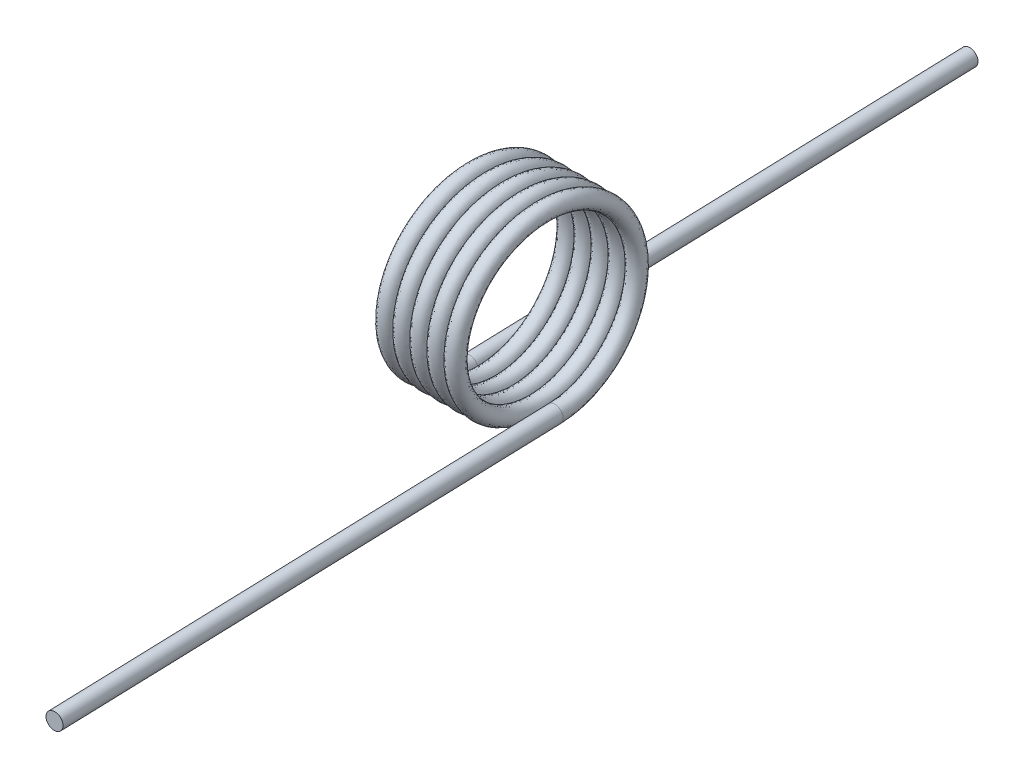
SolidWorks part; units mm, degrees
ref_plane "Front" through (0, 0, 0) normal (0, 0, 1) x (1, 0, 0)
ref_plane "Top" through (0, 0, 0) normal (0, 1, 0) x (1, 0, 0)
ref_plane "Right" through (0, 0, 0) normal (1, 0, 0) x (0, 0, -1)
sketch "Sketch1" plane through (0, 0, 0) normal (1, 0, 0) x (0, 0, -1)
  line L0 (0, 0) -> (0, -3.8354) construction
  line L1 (0, -3.8354) -> (0, -4.2418) construction
  line L2 (0, -4.2418) -> (0, -4.6482) construction
  circle A0 centre (0, 0) radius 3.8354 construction
  circle A1 centre (0, 0) radius 4.6482 construction
  circle A2 centre (0, 0) radius 4.2418
  circle A3 centre (0, -4.2418) radius 0.4064 construction
  circle A4 centre (0, 0) radius 3.175 construction
  dimension "Wire Dia" = 0.8128
  dimension "Spring OD" = 9.2964
  dimension "Max Rod OD" = 6.35
curve "Helix/Spiral1" pitch 0.8382 height 4.191 turns 5
ref_plane "Plane1" through (0, -4.2418, 0) normal (0.0314, 0, 0.9995) x (0.9995, 0, -0.0314)
sketch "Sketch2" plane through (0, -4.2418, 0) normal (0.0314, 0, 0.9995) x (0.9995, 0, -0.0314)
  circle A0 centre (0, 0) radius 0.4064
  dimension "D1" = 0.8128
sweep "Sweep1" add profiles "Sketch2" path "Helix/Spiral1"
sketch "Sketch3" plane through (0, 0, 0) normal (-0.0314, 0, -0.9995) x (-0.9995, 0, 0.0314)
  circle A1 centre (0, -4.2418) radius 0.4064
  circle A2 centre (0, -4.2418) radius 0.4064
  dimension "D1" = 0
extrude "Extrude1" add sketch "Sketch3" along normal blind 25.4
sketch "Sketch4" plane through (0.0041, 0, 0.1317) normal (0.0314, 0, 0.9995) x (0.9958, -0.0856, -0.0313)
  circle A1 centre (4.5367, -3.8676) radius 0.4064
  circle A2 centre (4.5367, -3.8676) radius 0.4064
  dimension "D1" = 0
extrude "Extrude2" add sketch "Sketch4" along normal blind 25.4
sketch "Sketch5" plane through (0, 0, 0) normal (1, 0, 0) x (0, 0, -1)
  circle A0 centre (0, 0) radius 3.175 construction
  circle A1 centre (0, 0) radius 3.175
equation "\"D4@Helix/Spiral1\"=\"Wire Dia@Sketch1\"+.001"
equation "\"D1@Sketch2\"=\"Wire Dia@Sketch1\""
equation "\"D1@Extrude2\"=\"Leg Length@Extrude1\""
